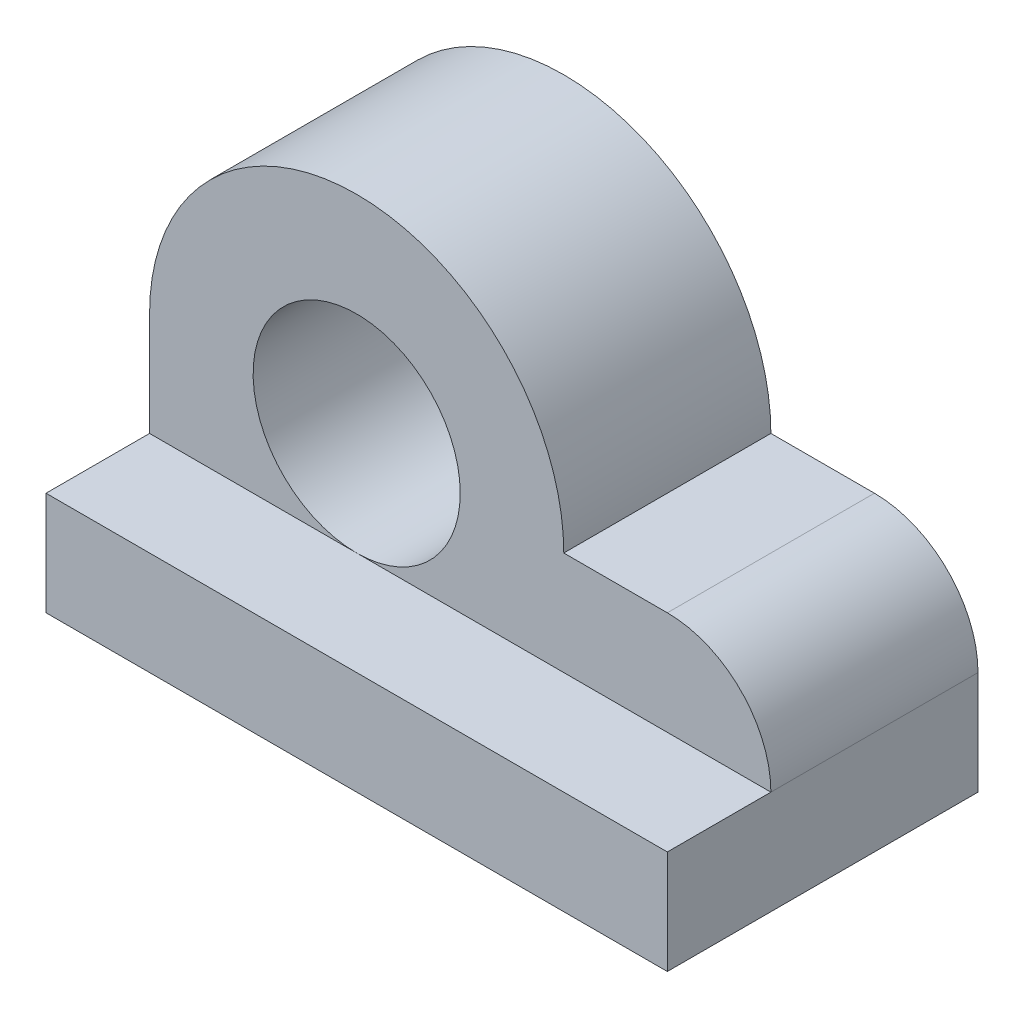
SolidWorks part; units mm, degrees
ref_plane "前基準面" through (0, 0, 0) normal (0, 0, 1) x (1, 0, 0)
ref_plane "上基準面" through (0, 0, 0) normal (0, 1, 0) x (1, 0, 0)
ref_plane "右基準面" through (0, 0, 0) normal (1, 0, 0) x (0, 0, -1)
sketch "草圖1" plane through (0, 0, 0) normal (0, 0, 1) x (1, 0, 0)
  line L0 (0, 10) -> (0, 20)
  line L1 (0, 0) -> (60, 0)
  line L2 (0, 0) -> (0, 10)
  line L3 (0, 10) -> (60, 10)
  line L4 (60, 0) -> (60, 10)
  line L5 (40, 20) -> (60, 20)
  line L6 (60, 20) -> (60, 10)
  circle A0 centre (20, 20) radius 5
  arc A1 (40, 20) -> (0, 20) centre (20, 20) ccw
  dimension "D4" = 10
  dimension "D3" = 10
  dimension "D5" = 20
  dimension "D6" = 10
  dimension "D1" = 60
  dimension "D2" = 10
extrude "填料-伸長1" add sketch "草圖1" along normal blind 30 contours L1 L4 L3 L2 region at (30, 5, 0)
extrude "填料-伸長2" add sketch "草圖1<3>" along normal blind 20 contours L5 A1 L0 L3 L6 A0 region at (25.2184, 22.0294, 0)
sketch "草圖1<3>" plane through (0, 0, 0) normal (0, 0, 1) x (1, 0, 0) same geometry as "草圖1"
fillet "圓角1" radius 10 1 edges at (60, 20, 10)
sketch "草圖2" plane through (0, 0, 20) normal (0, 0, 1) x (1, 0, 0)
  circle A0 centre (20, 20) radius 10
  dimension "D1" = 20
extrude "除料-伸長1" cut sketch "草圖2" against normal blind 20
